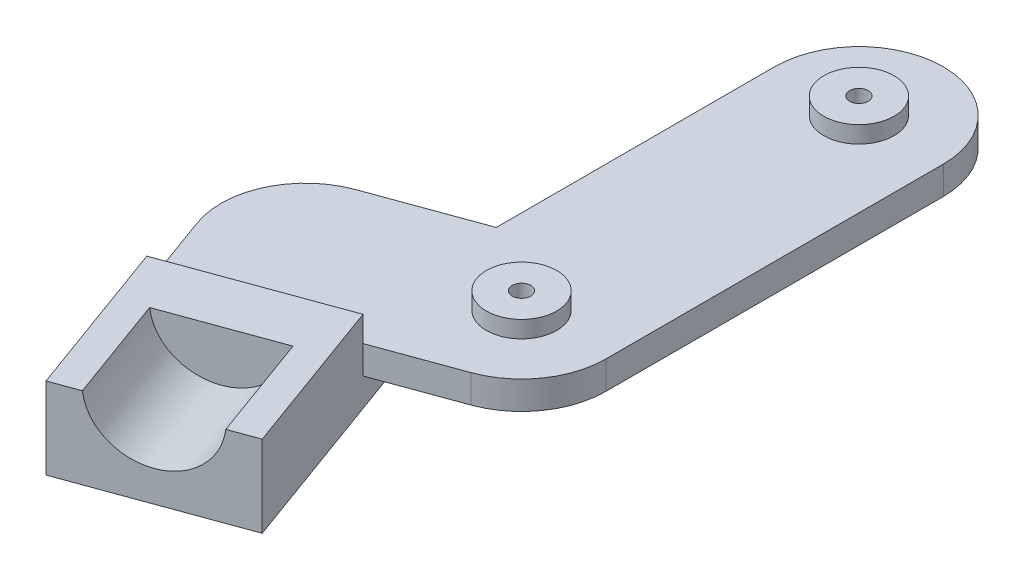
SolidWorks part; units mm, degrees
material "7075-T6 (SN)"
ref_plane "정면" through (0, 0, 0) normal (0, 0, 1) x (1, 0, 0)
ref_plane "윗면" through (0, 0, 0) normal (0, 1, 0) x (1, 0, 0)
ref_plane "우측면" through (0, 0, 0) normal (1, 0, 0) x (0, 0, -1)
sketch "스케치1" plane through (0, 0, 0) normal (0, 1, 0) x (1, 0, 0)
  line L0 (0, 0) -> (0, 60) construction
  line L2 (-15, 0) -> (-15, 60)
  line L3 (15, 0) -> (15, 60)
  arc A0 (-15, 0) -> (15, 0) centre (0, 0) ccw
  arc A1 (15, 60) -> (-15, 60) centre (0, 60) ccw
  point P5 (0, 30)
  dimension "D2" = 15
  dimension "D1" = 60
extrude "보스-돌출1" add sketch "스케치1" along normal blind 5
sketch "스케치2" plane through (0, 5, 0) normal (0, 1, 0) x (1, 0, 0)
  line L0 (0, 60) -> (0, 0) construction
  circle A0 centre (0, 60) radius 6.25
  circle A1 centre (0, 0) radius 6.25
  dimension "D2" = 12.5
  dimension "D3" = 12.5
  dimension "D1" = 60
extrude "보스-돌출2" add sketch "스케치2" along normal blind 3
hole_wizard "M4 탭을 위한 탭 드릴1" positions "스케치5" profile "스케치7" hole size "M4" standard "ISO"
sketch "스케치5" plane through (0, 8, 0) normal (0, 1, 0) x (1, 0, 0)
  point P0 (0, 0)
  point P3 (0, 60)
sketch "스케치7" plane through (0, 8, 0) normal (1, 0, 0) x (0, 0, 1)
  line L0 (0, 0) -> (0, 5.9914)
  line L1 (0, 5.9914) -> (1.65, 5)
  line L2 (1.65, 5) -> (1.65, 0)
  line L5 (1.65, 0) -> (0, 0)
  line L10 (0, 5.9914) -> (-1.65, 5) construction
  line L11 (0, -6.35) -> (0, 107.95) construction
  dimension "구멍 지름" = 3.3
  dimension "구멍 깊이" = 5
  dimension "드릴 각도" = 118
sketch "스케치9" plane through (0, 0, 0) normal (0, -1, 0) x (1, 0, 0)
  line L0 (0, 0) -> (-41.3824, 15.062) construction
  line L1 (-15, -60) -> (-15, 0) construction
  line L2 (0, 0) -> (-28.1908, 10.2606) construction
  line L3 (-5.1303, -14.0954) -> (-33.3211, -3.8348)
  line L4 (5.1303, 14.0954) -> (-23.0605, 24.356)
  arc A0 (-5.1303, -14.0954) -> (5.1303, 14.0954) centre (0, 0) ccw
  arc A1 (-23.0605, 24.356) -> (-33.3211, -3.8348) centre (-28.1908, 10.2606) ccw
  point P5 (-14.0954, 5.1303)
  dimension "D3" = 15
  dimension "D1" = 110
  dimension "D2" = 30
extrude "보스-돌출3" add sketch "스케치9" against normal blind 5
sketch "스케치10" plane through (0, 0, 0) normal (0, -1, 0) x (1, 0, 0)
  line L0 (-28.1908, 10.2606) -> (0, 0) construction
  line L3 (-42.2862, 15.3909) -> (-26.8953, 57.6771)
  line L6 (-28.1908, 10.2606) -> (-14.9216, 46.7173) construction
  line L7 (-14.0954, 5.1303) -> (1.2955, 47.4165)
  line L8 (-26.8953, 57.6771) -> (1.2955, 47.4165)
  arc A4 (-42.2862, 15.3909) -> (-14.0954, 5.1303) centre (-28.1908, 10.2606) ccw
  dimension "D2" = 90
  dimension "D3" = 45
  dimension "D1" = 30
extrude "보스-돌출4" add sketch "스케치10" against normal blind 5 and the other way blind 5
sketch "스케치11" plane through (0, 5, 0) normal (0, 1, 0) x (1, 0, 0)
  line L0 (-26.8953, -57.6771) -> (-42.2862, -15.3909) construction
  line L1 (1.2955, -47.4165) -> (-26.8953, -57.6771) construction
  line L2 (-8.9651, -19.2257) -> (1.2955, -47.4165) construction
  line L3 (-26.8953, -57.6771) -> (-37.1559, -29.4863)
  line L4 (1.2955, -47.4165) -> (-26.8953, -57.6771)
  line L5 (-8.9651, -19.2257) -> (1.2955, -47.4165)
  line L6 (-8.9651, -19.2257) -> (-37.1559, -29.4863)
extrude "보스-돌출5" add sketch "스케치11" along normal blind 4.5
sketch "스케치12" plane through (15.3909, 0, 42.2862) normal (0.342, 0, 0.9397) x (0.9397, 0, -0.342)
  line L0 (-45, 9.5) -> (-15, 9.5) construction
  line L1 (-48.0608, 10.5) -> (-11.833, 10.5) construction
  line L2 (-45, -5) -> (-45, 9.5) construction
  circle A0 centre (-30, 10.5) radius 10
  dimension "D1" = 20
  dimension "D2" = 1
  dimension "D3" = 15
extrude "컷-돌출1" cut sketch "스케치12" against normal blind 20
